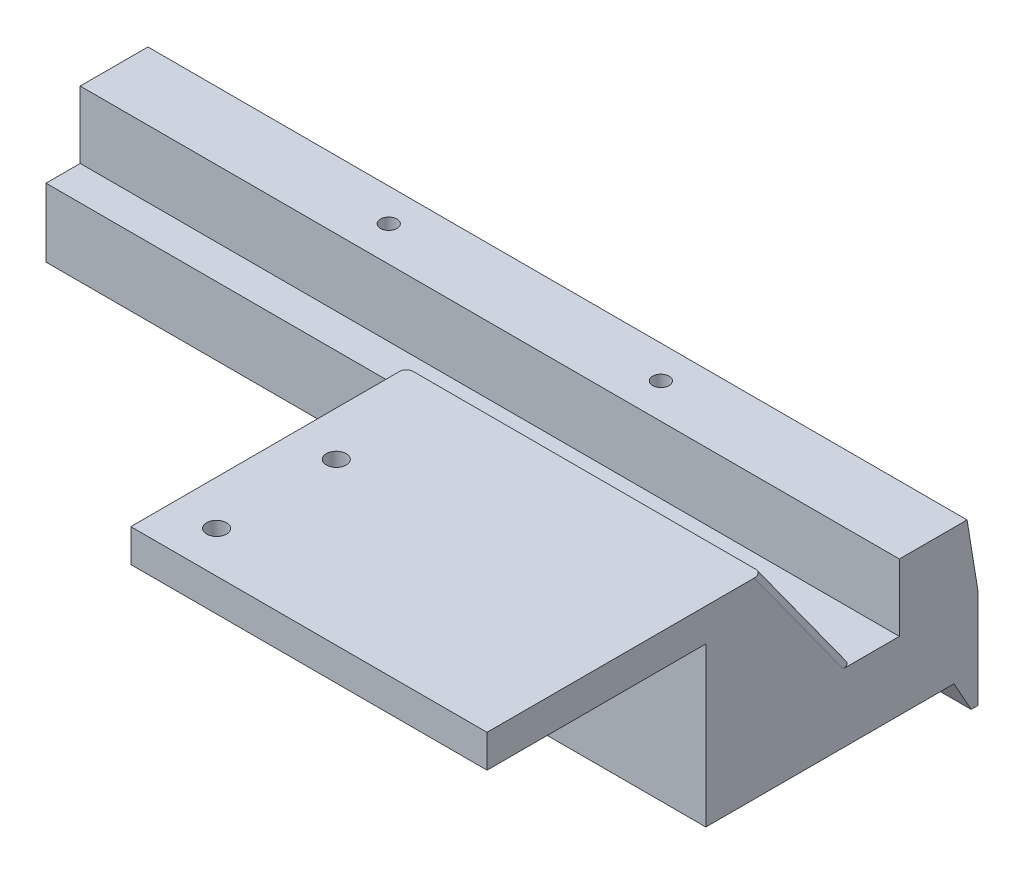
SolidWorks part; units mm, degrees
ref_plane "Płaszczyzna przednia" through (0, 0, 0) normal (0, 0, 1) x (1, 0, 0)
ref_plane "Płaszczyzna górna" through (0, 0, 0) normal (0, 1, 0) x (1, 0, 0)
ref_plane "Płaszczyzna prawa" through (0, 0, 0) normal (1, 0, 0) x (0, 0, -1)
sketch "Szkic1" plane through (0, 0, 0) normal (0, 0, 1) x (1, 0, 0)
  line L1 (-58.3066, 32.0248) -> (61.4934, 32.0248)
  line L2 (-58.3066, 32.0248) -> (-58.3066, 22.0248)
  line L3 (-58.3066, 22.0248) -> (61.4934, 22.0248)
  line L4 (61.4934, 32.0248) -> (61.4934, 22.0248)
  dimension "D1" = 119.8
  dimension "D2" = 10
extrude "Dodanie-wyciągnięcie2" add sketch "Szkic1" along normal blind 38.3 contours L2 L3 L4 L1
sketch "Szkic21" plane through (0, 32.0248, 0) normal (0, 1, 0) x (1, 0, 0)
  line L0 (61.4934, -38.3) -> (61.4934, 0) construction
  line L1 (-58.3066, 0) -> (61.4934, 0)
  line L2 (-58.3066, 0) -> (-58.3066, -10)
  line L3 (-58.3066, -10) -> (61.4934, -10)
  line L4 (61.4934, 0) -> (61.4934, -10)
extrude "Dodanie-wyciągnięcie3" add sketch "Szkic21" along normal blind 9.8
sketch "Szkic22" plane through (0, 22.0248, 0) normal (0, -1, 0) x (1, 0, 0)
  line L0 (-58.3066, 4.88) -> (-18.3066, 4.88) construction
  line L1 (-58.3066, 38.3) -> (-58.3066, 0) construction
  line L2 (-18.3066, 4.88) -> (21.4934, 4.88) construction
  line L3 (21.4934, 4.88) -> (61.4934, 4.88) construction
  line L4 (61.4934, 38.3) -> (61.4934, 0) construction
  line L5 (1.9729, 4.88) -> (1.9729, 0) construction
  line L6 (-58.3066, 0) -> (61.4934, 0) construction
hole_wizard "Pogłębienie walcowe pod M2 wkręt do części metalowych z łbem stożkowym ściętym2" positions "Szkic23" profile "Szkic24" counterbore size "M2" standard "Ansi Metric" end condition through all
sketch "Szkic23" plane through (0, 22.0248, 0) normal (0, -1, 0) x (-1, 0, 0)
  point P0 (-21.4934, -4.88)
  point P3 (18.3066, -4.88)
sketch "Szkic24" plane through (21.4934, 22.0248, 4.88) normal (1, 0, 0) x (0, 0, -1)
  line L0 (0, 0) -> (0, 19.8)
  line L1 (0, 19.8) -> (1.2, 19.8)
  line L3 (1.2, 19.8) -> (1.2, 1.6)
  line L4 (1.2, 1.6) -> (2.5, 1.6)
  line L5 (2.5, 1.6) -> (2.5, 0)
  line L7 (2.5, 0) -> (0, 0)
  line L11 (0, -6.35) -> (0, 107.95) construction
  dimension "Średnica otworu na wylot" = 2.4
  dimension "Głębokość otworu na wylot" = 19.8
  dimension "Średnica pogłębienia walcowego" = 5
  dimension "Głębokość pogłębienia walcowego" = 1.6
sketch "Szkic28" plane through (0, 22.0248, 0) normal (0, -1, 0) x (1, 0, 0)
  line L0 (36.4934, 0) -> (36.4934, 23.3) construction
  line L1 (-58.3066, 0) -> (61.4934, 0) construction
  line L2 (36.4934, 23.3) -> (61.4934, 23.3) construction
  line L3 (61.4934, 38.3) -> (61.4934, 0) construction
  line L4 (-58.3066, 38.3) -> (61.4934, 38.3) construction
  circle A0 centre (36.4934, 23.3) radius 11.1
  dimension "D1" = 15
extrude "Wytnij-wyciągnięcie1" cut sketch "Szkic28" against normal blind 7.2
sketch "Szkic31" plane through (61.4934, 0, 0) normal (1, 0, 0) x (0, 0, -1)
  line L0 (-10, 32.0248) -> (-10, 71.9248)
  line L2 (0, 41.2325) -> (0, 32.0248)
  line L6 (0, 41.8248) -> (0, 22.0248) construction
  line L8 (0, 32.0248) -> (1.5, 32.0248)
  line L10 (-10, 32.0248) -> (1.5, 32.0248)
  line L12 (-10, 71.9248) -> (-5, 71.9248)
  line L13 (-5, 71.9248) -> (1.5, 32.0248)
  line L14 (-0.4105, 43.7521) -> (0.2752, 39.543)
  line L15 (0.2752, 39.543) -> (3.3905, 40.0505)
  line L16 (3.3905, 40.0505) -> (-0.4105, 43.7521)
  line M5 (0, 22.0248) -> (0, 41.8248)
  line M6 (0, 41.8248) -> (-10, 41.8248)
extrude "Wytnij-wyciągnięcie4" cut sketch "Szkic31" against normal blind 124.8 contours L13 M6 M5 region at (61.4934, 41.6274, 0.0322)
extrude "Dodanie-wyciągnięcie5" add sketch "Szkic31<5>" against normal blind 119.8 contours L13 L8 M5 region at (61.4934, 35.0941, -0.5)
sketch "Szkic31<5>" plane through (61.4934, 0, 0) normal (1, 0, 0) x (0, 0, -1) same geometry as "Szkic31"
sketch "Szkic34" plane through (0, 0, 0) normal (0, 0, -1) x (-1, 0, 0)
  line L1 (-61.4934, 32.0248) -> (58.3066, 32.0248)
  line L2 (-61.4934, 32.0248) -> (-61.4934, 22.0248)
  line L3 (-61.4934, 22.0248) -> (58.3066, 22.0248)
  line L4 (58.3066, 32.0248) -> (58.3066, 22.0248)
extrude "Dodanie-wyciągnięcie6" add sketch "Szkic34" along normal blind 1.5
sketch "Szkic37" plane through (0, 32.0248, 0) normal (0, 1, 0) x (1, 0, 0)
  line L1 (61.4934, -38.3) -> (9.3934, -38.3)
  line L2 (61.4934, -38.3) -> (61.4934, -30)
  line L3 (61.4934, -30) -> (9.3934, -30)
  line L4 (9.3934, -38.3) -> (9.3934, -30)
extrude "Dodanie-wyciągnięcie8" add sketch "Szkic37" along normal blind 18
sketch "Szkic38" plane through (0, 0, 38.3) normal (0, 0, 1) x (1, 0, 0)
  line L0 (61.4934, 50.0248) -> (61.4934, 22.0248) construction
  line L1 (9.3934, 50.0248) -> (61.4934, 50.0248)
  line L2 (9.3934, 50.0248) -> (9.3934, 45.2248)
  line L3 (9.3934, 45.2248) -> (61.4934, 45.2248)
  line L4 (61.4934, 50.0248) -> (61.4934, 45.2248)
extrude "Dodanie-wyciągnięcie11" add sketch "Szkic38" along normal blind 32
sketch "Szkic40" plane through (0, 45.2248, 0) normal (0, -1, 0) x (1, 0, 0)
  line L0 (9.3934, 44.15) -> (61.4934, 44.15) construction
  line L1 (9.3934, 70.3) -> (9.3934, 38.3) construction
  line L2 (61.4934, 70.3) -> (61.4934, 38.3) construction
  line L3 (9.3934, 38.3) -> (61.4934, 38.3) construction
  line L4 (49.3934, 44.15) -> (49.3934, 38.3) construction
  line L5 (9.3934, 66.65) -> (61.4934, 66.65) construction
  line L6 (9.3934, 70.3) -> (61.4934, 70.3) construction
  line L7 (9.3934, 55.4) -> (61.4934, 55.4) construction
  line L8 (39.019, 44.15) -> (44.019, 44.15)
  line L9 (39.019, 44.15) -> (39.019, 42.65)
  line L10 (39.019, 42.65) -> (44.019, 42.65)
  line L11 (44.019, 44.15) -> (44.019, 42.65)
  line L12 (32.3245, 66.65) -> (32.3245, 55.4) construction
  line L13 (32.3245, 55.4) -> (32.3245, 44.15) construction
  point P22 (0, 0)
  point P24 (0, 0)
  point P25 (0, 0)
  dimension "D1" = 11.25
  dimension "D2" = 12.1
  dimension "D3" = 3.65
ref_plane "Płaszczyzna1" through (0, 43.2248, 0) normal (0, -1, 0) x (-1, 0, 0)
sketch "Szkic41" plane through (0, 43.2248, 0) normal (0, -1, 0) x (-1, 0, 0)
  line L0 (-39.019, -42.65) -> (-44.019, -42.65) construction
  line L1 (-43.4902, -42.65) -> (-39.5477, -42.65)
  line L2 (-43.4902, -42.65) -> (-43.4902, -44.15)
  line L3 (-43.4902, -44.15) -> (-39.5477, -44.15)
  line L4 (-39.5477, -42.65) -> (-39.5477, -44.15)
  line L5 (-39.019, -44.15) -> (-44.019, -44.15) construction
  line L6 (-44.019, -43.4) -> (-43.4902, -43.4) construction
  line L11 (-44.019, -44.15) -> (-44.019, -42.65) construction
  line L12 (-39.5477, -43.4) -> (-39.019, -43.4) construction
  line L14 (-39.019, -44.15) -> (-39.019, -42.65) construction
loft "Wyciągnięcie po profilach5" add profiles "Szkic40", "Szkic41" connector at (39.019, 45.2248, 42.65) connector at (39.5477, 43.2248, 42.65)
fillet "Zaokrąglenie5" radius 0.5 8 edges
pattern_linear "Szyk liniowy2" count 2 spacing 24.2 along (0, 0, 1) of "Zaokrąglenie5", "Wyciągnięcie po profilach5"
sketch "Szkic43" plane through (0, 45.2248, 0) normal (0, -1, 0) x (1, 0, 0)
  line L0 (9.3934, 64.25) -> (15.8934, 64.25) construction
  line L1 (9.3934, 70.3) -> (9.3934, 38.3) construction
  line L3 (9.3934, 46.75) -> (15.8934, 46.75) construction
  line L4 (15.8934, 70.3) -> (15.8934, 64.25) construction
  line L7 (9.3934, 70.3) -> (61.4934, 70.3) construction
  line L8 (15.8934, 64.25) -> (15.8934, 46.75) construction
  line L9 (15.8934, 46.75) -> (15.8934, 38.3) construction
  line L10 (9.3934, 38.3) -> (61.4934, 38.3) construction
  line L11 (15.8934, 64.25) -> (61.4934, 64.25) construction
  line L12 (61.4934, 70.3) -> (61.4934, 38.3) construction
  line L13 (15.8934, 46.75) -> (61.4934, 46.75) construction
  line L14 (43.5018, 44.15) -> (39.5361, 44.15) construction
  line L15 (41.519, 44.15) -> (41.519, 46.75)
  line L16 (41.519, 46.75) -> (41.519, 64.25)
  line L17 (41.519, 64.25) -> (41.519, 66.85)
  line L18 (39.5361, 66.85) -> (43.5018, 66.85) construction
  point P20 (0, 0)
  point P25 (0, 0)
  point P26 (0, 0)
  point P27 (0, 0)
  dimension "D1" = 8.45
  dimension "D2" = 45.6
  dimension "18.1" = 17.5
hole_wizard "Otwór pod śrubę M2.51" positions "Szkic44" profile "Szkic45" hole size "M2.5" standard "ISO" end condition through all
sketch "Szkic44" plane through (0, 45.2248, 0) normal (0, -1, 0) x (-1, 0, 0)
  point P0 (-15.8934, -46.75)
  point P3 (-15.8934, -64.25)
sketch "Szkic45" plane through (15.8934, 45.2248, 46.75) normal (1, 0, 0) x (0, 0, -1)
  line L0 (0, 0) -> (0, 4.8)
  line L1 (0, 4.8) -> (1.45, 4.8)
  line L2 (1.45, 4.8) -> (1.45, 0)
  line L5 (1.45, 0) -> (0, 0)
  line L11 (0, -6.35) -> (0, 107.95) construction
  dimension "Średnica otworu na wylot" = 2.9
  dimension "Głębokość otworu na wylot" = 4.8
sketch "Szkic52" plane through (61.4934, 0, 0) normal (1, 0, 0) x (0, 0, -1)
  line L0 (-30, 50.0248) -> (-17, 32.0248)
  line L1 (-30, 32.0248) -> (-10, 32.0248) construction
  line L2 (-30, 50.0248) -> (-30, 32.0248) construction
  dimension "D1" = 13
rib "Żebro7" sketch "Szkic52" sketch "Szkic52" thickness 3 extrusion direction parallel to sketch draft on no parameters "D1"=3
fillet "Zaokrąglenie7" radius 1 2 edges at (61.4934, 41.0248, 23.5) (58.4934, 41.0248, 23.5)
pattern_linear "Szyk liniowy6" count 5 spacing 12.25 along (-1, 0, 0) of "Żebro7", "Zaokrąglenie7"
fillet "Zaokrąglenie8" radius 1 1 edges at (9.3934, 41.0248, 30)
sketch "Szkic53" plane through (0, 0, 38.3) normal (0, 0, 1) x (1, 0, 0)
  line L1 (9.3934, 32.0248) -> (-58.3066, 32.0248)
  line L2 (9.3934, 32.0248) -> (9.3934, 22.0248)
  line L3 (9.3934, 22.0248) -> (-58.3066, 22.0248)
  line L4 (-58.3066, 32.0248) -> (-58.3066, 22.0248)
extrude "Wytnij-wyciągnięcie5" cut sketch "Szkic53" against normal blind 23.3
sketch "Szkic54" plane through (61.4934, 0, 0) normal (1, 0, 0) x (0, 0, -1)
  line L0 (-2, 22.0248) -> (1.5, 22.0248)
  line L1 (1.5, 17.5248) -> (0.5, 17.5248)
  line L2 (-4.88, 22.0248) -> (0, 22.0248) construction
  line L3 (-38.3, 22.0248) -> (1.5, 22.0248) construction
  line L4 (1.5, 22.0248) -> (1.5, 17.5248)
  line L6 (0.5, 17.5248) -> (-2, 22.0248)
extrude "Dodanie-wyciągnięcie12" add sketch "Szkic54" against normal blind 119.8
